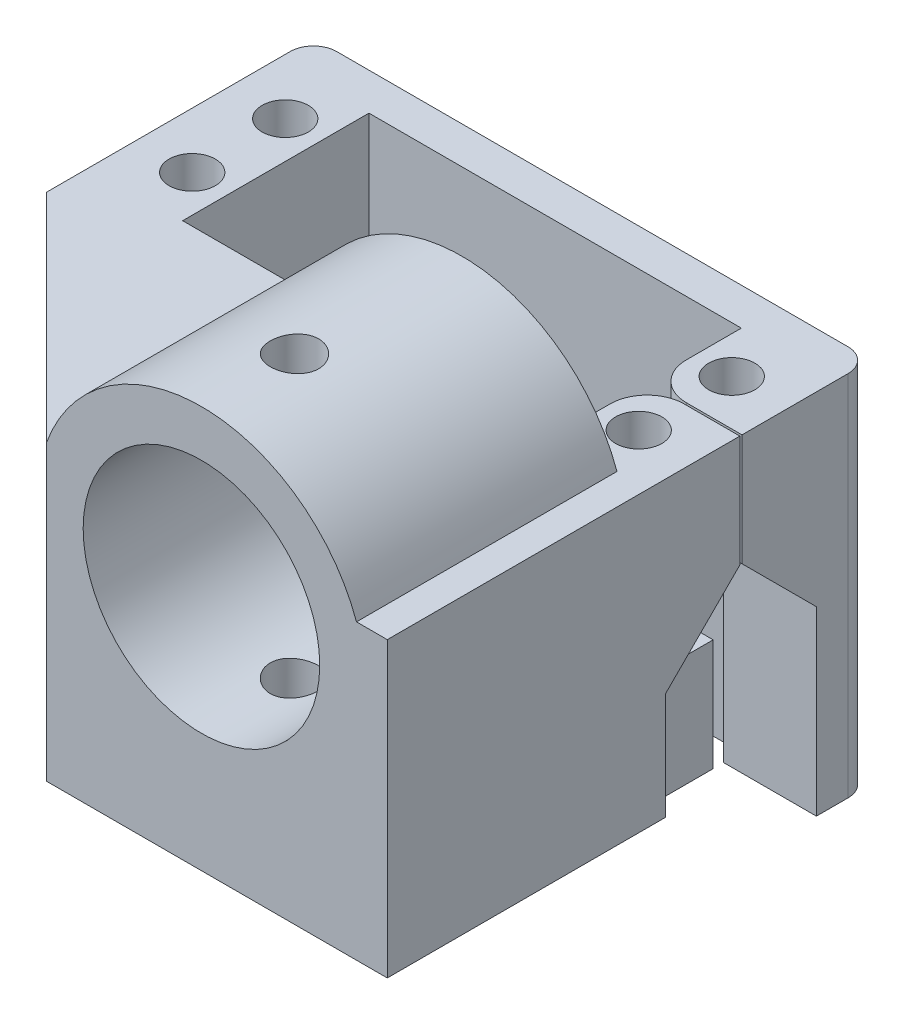
SolidWorks part; units mm, degrees
ref_plane "Front Plane" through (0, 0, 0) normal (0, 0, 1) x (1, 0, 0)
ref_plane "Top Plane" through (0, 0, 0) normal (0, 1, 0) x (1, 0, 0)
ref_plane "Right Plane" through (0, 0, 0) normal (1, 0, 0) x (0, 0, -1)
sketch "Sketch1" plane through (0, 0, 0) normal (0, 1, 0) x (1, 0, 0)
  line L0 (20.015, 0) -> (27.985, 0)
  line L1 (27.985, -14.015) -> (-27.985, -14.015)
  line L2 (27.985, -14.015) -> (27.985, 14.015)
  line L3 (27.985, 14.015) -> (-27.985, 14.015)
  line L4 (-27.985, -14.015) -> (-27.985, 14.015)
  line L5 (27.985, -14.015) -> (-27.985, 14.015) construction
  line L6 (27.985, 14.015) -> (-27.985, -14.015) construction
  line L7 (20.015, -10.015) -> (-20.015, -10.015)
  line L8 (20.015, -10.015) -> (20.015, 10.015)
  line L9 (20.015, 10.015) -> (-20.015, 10.015)
  line L10 (-20.015, -10.015) -> (-20.015, 10.015)
  line L11 (20.015, -10.015) -> (-20.015, 10.015) construction
  line L12 (20.015, 10.015) -> (-20.015, -10.015) construction
  line L13 (24, -5) -> (-24, -5) construction
  line L14 (24, -5) -> (24, 5) construction
  line L15 (24, 5) -> (-24, 5) construction
  line L16 (-24, -5) -> (-24, 5) construction
  line L17 (24, -5) -> (-24, 5) construction
  line L18 (24, 5) -> (-24, -5) construction
  line L19 (-27.985, -14.015) -> (-27.985, -18.015)
  line L20 (-27.985, -18.015) -> (27.985, -18.015)
  line L21 (27.985, -18.015) -> (27.985, -14.015)
  line L22 (27.985, 14.015) -> (29.985, 14.015)
  line L23 (29.985, 14.015) -> (29.985, 0.115)
  line L24 (29.985, 0.115) -> (24, 0.115)
  line L25 (27.985, -14.015) -> (29.985, -14.015)
  line L26 (29.985, -14.015) -> (29.985, -0.115)
  line L27 (29.985, -0.115) -> (24, -0.115)
  line L28 (27.985, -18.015) -> (29.985, -18.015)
  line L29 (29.985, -18.015) -> (29.985, -14.015)
  line L30 (-27.985, 14.015) -> (-29.985, 14.015)
  line L31 (-29.985, 14.015) -> (-29.985, -18.015)
  line L32 (-29.985, -18.015) -> (-27.985, -18.015)
  line L33 (-20.015, -18.015) -> (-20.015, -78.515)
  line L34 (-20.015, -78.515) -> (17.515, -78.515)
  line L35 (17.515, -78.515) -> (17.515, -88.485)
  line L36 (17.515, -88.485) -> (-29.985, -88.485)
  line L37 (-29.985, -88.485) -> (-29.985, -18.015)
  line L38 (-20.015, -78.515) -> (-29.985, -78.515) construction
  line L39 (-37.485, 7.6) -> (-29.985, 7.6)
  line L40 (-37.485, -7.6) -> (-29.985, -7.6)
  line L41 (-37.485, 0) -> (-29.985, 0) construction
  circle A1 centre (24, 5) radius 2.485
  circle A2 centre (24, -5) radius 2.485
  circle A3 centre (-24, -5) radius 2.485
  circle A4 centre (-24, 5) radius 2.485
  arc A5 (20.015, 4.1) -> (27.985, 4.1) centre (24, 4.1) ccw
  arc A6 (20.015, -4.1) -> (27.985, -4.1) centre (24, -4.1) cw
  circle A7 centre (-37.485, 0) radius 2.6
  arc A8 (-37.485, 7.6) -> (-37.485, -7.6) centre (-37.485, 0) ccw
  point P0 (0, 0)
  point P6 (0, 0)
  point P11 (0, 0)
  dimension "D1" = 4.97
  dimension "D7" = 4.1
  dimension "D8" = 4.1
  dimension "D14" = 5.2
  dimension "D15" = 5
  dimension "D16" = 7.5
  dimension "D2" = 48
  dimension "D3" = 4
  dimension "D4" = 40.03
  dimension "D5" = 20.03
  dimension "D6" = 10
  dimension "D9" = 4
  dimension "D10" = 2
  dimension "D11" = 2
  dimension "D12" = 60.5
  dimension "D13" = 47.5
extrude "Boss-Extrude1" add sketch "Sketch1" along normal mid plane 12 contours A6 L8 L7 L10 L9 A5 L2 L3 L4 L1 A4 A3 A2 A1 | L20 L21 L1 L19 | L24 L23 L22 L2 | L26 L27 L2 L25 | L27 A6 L2 | A5 L24 L2 | L28 L29 L25 L21 | L31 L32 L19 L4 L30 region at (21.6248, 0, 1.7248) region at (28.985, 0, 7.065) region at (27.0949, 0, 1.0051) region at (27.0949, 0, -1.0051) region at (28.985, 0, -7.065) region at (0, 0, 16.015) region at (28.985, 0, 16.015) region at (-28.985, 0, 2)
sketch "Sketch2" plane through (0, -6, 0) normal (0, -1, 0) x (1, 0, 0)
  circle A0 centre (24, -5) radius 2.485 construction
  circle A1 centre (24, 5) radius 2.485 construction
  circle A2 centre (-24, -5) radius 2.485 construction
  circle A3 centre (-24, 5) radius 2.485 construction
  circle A4 centre (24, -5) radius 2.485
  circle A5 centre (24, 5) radius 2.485
  circle A6 centre (-24, -5) radius 2.485
  circle A7 centre (-24, 5) radius 2.485
extrude "Boss-Extrude2" add sketch "Sketch2" against normal offset from surface (2 mm away) 10 up to face at (10.4535, 6, 0.5714)
sketch "Sketch3" plane through (0, 0, 18.015) normal (0, 0, 1) x (1, 0, 0)
  line L0 (10.015, 0) -> (-10.485, 0) construction
  line L1 (-10.485, 0) -> (-14.485, 0) construction
  circle A2 centre (10.015, 0) radius 1.6
  circle A3 centre (-14.485, 0) radius 1.6
  dimension "D3" = 3.2
  dimension "D4" = 3.2
  dimension "D1" = 4
  dimension "D2" = 20.5
  dimension "D5" = 10
extrude "Cut-Extrude1" [suppressed] cut sketch "Sketch3" against normal blind 10 contours A2
sketch "Sketch4" [suppressed] plane through (0, 0, -14.015) normal (0, 0, -1) x (-1, 0, 0)
  line L4 (-29.985, -6) -> (29.985, -6)
  line L5 (29.985, -6) -> (29.985, 6)
  line L6 (29.985, 6) -> (-29.985, 6)
  line L7 (-29.985, 6) -> (-29.985, -6)
  line L8 (-29.985, -6) -> (29.985, -6)
  line L10 (29.985, 6) -> (-29.985, 6)
  line L12 (-29.985, 6) -> (-29.985, -6)
  line L13 (29.985, -6) -> (29.985, 6)
  circle A2 centre (-10.015, 0) radius 3
  circle A6 centre (-10.015, 0) radius 1.6 construction
  circle A7 centre (-10.015, 0) radius 1.6 construction
  dimension "D2" = 6
  dimension "D1" = 0
extrude "Cut-Extrude2" [suppressed] cut sketch "Sketch4" against normal offset from surface (28.03 mm away) 4 contours A2 offset beyond the face yes
sketch "Sketch5" plane through (0, 0, 0) normal (1, 0, 0) x (0, 0, -1)
  line L0 (-18.015, -6) -> (-10.015, -6)
  line L1 (-10.015, -6) -> (-10.015, -21.5)
  line L2 (-10.015, -21.5) -> (6.985, -21.5)
  line L3 (6.985, -21.5) -> (6.985, -33.5)
  line L4 (6.985, -33.5) -> (-18.015, -33.5)
  line L5 (-18.015, -33.5) -> (-18.015, -6)
  line L7 (-10.015, 6) -> (10.015, 6) construction
  dimension "D1" = 27.5
  dimension "D2" = 12
  dimension "D3" = 25
extrude "Boss-Extrude3" add sketch "Sketch5" along normal up to surface (20.015 mm away) up to face at (20.015, 0, 7.0575)
sketch "Sketch6" plane through (0, -33.5, 0) normal (0, -1, 0) x (1, 0, 0)
  line L0 (0, 0) -> (10.015, 0) construction
  line L1 (20.015, -4.1) -> (20.015, -10.015) construction
  circle A0 centre (10.015, 0) radius 2.485
  dimension "D2" = 4.97
  dimension "D1" = 10
extrude "Cut-Extrude3" cut sketch "Sketch6" against normal blind 10
sketch "Sketch10" plane through (0, 0, 18.015) normal (0, 0, 1) x (1, 0, 0)
  circle A0 centre (-14.485, 0) radius 1.485
  dimension "D1" = 2.97
extrude "Cut-Extrude6" [suppressed] cut sketch "Sketch10" against normal offset from surface 2 and the other way through all
sketch "Sketch11" plane through (0, 0, 18.015) normal (0, 0, 1) x (1, 0, 0)
  line L1 (10.0075, 0) -> (10.0075, 17.715) construction
  line L2 (20.015, -33.5) -> (20.015, -6) construction
  line L3 (0, -6) -> (0, -33.5) construction
  line L4 (10.0075, 0) -> (-7.7075, 0) construction
  line L5 (-29.985, 6) -> (29.985, 6) construction
  line L6 (-29.985, -6) -> (0, -6) construction
  circle A0 centre (10.0075, 0) radius 12.715
  circle A1 centre (10.0075, 0) radius 17.715
  line M2 (0, -6) -> (0, -33.5)
  line M4 (20.015, -33.5) -> (20.015, -6)
  line M8 (29.985, 6) -> (-29.985, 6)
  line M10 (-29.985, -6) -> (0, -6)
  dimension "D1" = 25.43
  dimension "D2" = 5
extrude "Boss-Extrude4" add sketch "Sketch11" against normal up to surface (8 mm away) contours A0 M2 M4 | A1 A0 M2 M4 | A0 M4 | A1 A0 M4 | L1 A0 A1 | A0 M2 | A1 A0 M10 M2 | A0 L1 A1 M10 | A0 M8 | A1 A0 M8 region at (10.0383, -2.3315, 18.015) region at (24.003, -3.2734, 18.015) region at (10.0075, 8.7579, 18.015) region at (10.0075, 13.0683, 18.015) region at (10.0075, -13.879, 18.015) region at (-4.7808, 0, 18.015) region at (-2.5393, -9.2557, 18.015) region at (-0.4138, -6.6334, 18.015) up to face at (2.8593, -7, 10.015)
extrude "Boss-Extrude5" add sketch "Sketch11<3>" along normal blind 20 contours A1 A0 M2 M4 | A1 A0 M4 | L1 A0 A1 | A0 L1 A1 M10 | A1 A0 M10 M2 | A1 A0 M8 region at (24.003, -3.2734, 18.015) region at (10.0075, 13.0683, 18.015) region at (10.0075, -13.879, 18.015) region at (-4.7808, 0, 18.015) region at (-2.5393, -9.2557, 18.015)
sketch "Sketch11<3>" plane through (0, 0, 18.015) normal (0, 0, 1) x (1, 0, 0) same geometry as "Sketch11"
sketch "Sketch12" plane through (0, -33.5, 0) normal (0, -1, 0) x (1, 0, 0)
  line L0 (-6.6605, 10.015) -> (-20.015, 10.015) construction
  line L1 (-7.7075, 38.015) -> (27.7225, 38.015)
  line L2 (-7.7075, 38.015) -> (-7.7075, 10.015)
  line L3 (-7.7075, 10.015) -> (27.7225, 10.015)
  line L4 (27.7225, 38.015) -> (27.7225, 10.015)
extrude "Boss-Extrude6" [suppressed] add sketch "Sketch12" against normal up to surface (33.5 mm away)
sketch "Sketch13" plane through (0, 0, 38.015) normal (0, 0, 1) x (1, 0, 0)
  line L3 (0, -14.6175) -> (0, -33.5)
  line L4 (0, -33.5) -> (20.015, -33.5)
  line L5 (20.015, -33.5) -> (20.015, -14.6175)
  line L6 (0, -14.6175) -> (0, -33.5)
  line L7 (0, -33.5) -> (20.015, -33.5)
  line L8 (20.015, -33.5) -> (20.015, -14.6175)
  line L9 (-6.6605, 6) -> (-29.985, 6)
  line L10 (-29.985, 6) -> (-29.985, -6)
  line L11 (-29.985, -6) -> (-6.6605, -6)
  line L12 (-6.6605, 6) -> (-29.985, 6)
  line L13 (-29.985, 6) -> (-29.985, -6)
  line L14 (-29.985, -6) -> (-6.6605, -6)
  line L15 (26.6755, -6) -> (29.985, -6)
  line L16 (29.985, -6) -> (29.985, 6)
  line L17 (29.985, 6) -> (26.6755, 6)
  line L18 (26.6755, -6) -> (29.985, -6)
  line L19 (29.985, -6) -> (29.985, 6)
  line L20 (29.985, 6) -> (26.6755, 6)
  circle A1 centre (10.0075, 0) radius 17.715
  circle A2 centre (10.0075, 0) radius 17.715
  arc A3 (0, -14.6175) -> (20.015, -14.6175) centre (10.0075, 0) ccw
  arc A4 (0, -14.6175) -> (20.015, -14.6175) centre (10.0075, 0) ccw
  arc A5 (-6.6605, 6) -> (-6.6605, -6) centre (10.0075, 0) ccw
  arc A6 (-6.6605, 6) -> (-6.6605, -6) centre (10.0075, 0) ccw
  arc A7 (26.6755, -6) -> (26.6755, 6) centre (10.0075, 0) ccw
  arc A8 (26.6755, -6) -> (26.6755, 6) centre (10.0075, 0) ccw
  circle M6 centre (10.0075, 0) radius 17.715
  dimension "D1" = 0
  dimension "D2" = 0
  dimension "D3" = 0
  dimension "D4" = 0
extrude "Boss-Extrude7" add sketch "Sketch13" against normal up to surface (20 mm away) contours L7 L8 L6 M6 | L13 L14 L12 M6 | L19 L20 L18 M6 region at (10.0075, -25.0861, 38.015) region at (-18.6717, 0, 38.015) region at (28.6628, 0, 38.015) up to face at (10.0075, -24.8331, 18.015)
sketch "Sketch14" plane through (0, 6, 0) normal (0, 1, 0) x (1, 0, 0)
  line L0 (-6.6605, -38.015) -> (-29.985, -14.6905)
  line L1 (-29.985, 14.015) -> (-29.985, -38.015) construction
  line L2 (-6.6605, -38.015) -> (-29.985, -38.015) construction
  line L3 (-6.6605, -38.015) -> (-29.985, -38.015)
  line L4 (-29.985, 14.015) -> (-29.985, -38.015)
  line M11 (-29.985, 14.015) -> (-29.985, -38.015)
  line M12 (-29.985, -38.015) -> (-6.6605, -38.015)
  dimension "D1" = 45
extrude "Cut-Extrude7" cut sketch "Sketch14" against normal through all both and the other way through all contours L0 M12 M11 region at (-22.2102, 6, 30.2402)
sketch "Sketch15" plane through (20.015, 0, 0) normal (1, 0, 0) x (0, 0, -1)
  line L0 (-38.015, -14.6175) -> (-19.1325, -33.5)
  line L1 (6.985, -33.5) -> (-38.015, -33.5) construction
  line L2 (-38.015, -33.5) -> (-38.015, -14.6175) construction
  line L3 (6.985, -33.5) -> (-38.015, -33.5)
  line L4 (-38.015, -33.5) -> (-38.015, -14.6175)
  line M5 (-38.015, -14.6175) -> (-38.015, -33.5)
  line M6 (-38.015, -33.5) -> (6.985, -33.5)
  dimension "D1" = 45
extrude "Cut-Extrude8" cut sketch "Sketch15" against normal through all both contours L0 M5 M6 region at (20.015, -27.2058, 31.7208)
fillet "Fillet1" radius 2.5 2 edges at (29.985, 0, -14.015) (-29.985, 0, -14.015)
sketch "Sketch16" plane through (0, 0, 0) normal (0, 1, 0) x (1, 0, 0)
  line L0 (-2.7075, -38.015) -> (22.7225, -38.015) construction
  line L1 (-2.7075, -18.015) -> (22.7225, -18.015) construction
  line L2 (-2.7075, -38.015) -> (22.7225, -38.015)
  line L3 (-2.7075, -18.015) -> (22.7225, -18.015)
  line L4 (10.0075, -18.015) -> (10.0075, -38.015) construction
  circle A0 centre (10.0075, -28.015) radius 2.6
  dimension "D1" = 5.2
extrude "Cut-Extrude9" cut sketch "Sketch16" against normal through all both and the other way through all contours A0
sketch "Sketch17" plane through (0, -33.5, 0) normal (0, -1, 0) x (1, 0, 0)
  circle A0 centre (10.0075, 28.015) radius 5.4369
  circle A1 centre (10.0075, 28.015) radius 2.6 construction
  circle A2 centre (10.0075, 28.015) radius 2.6
extrude "Cut-Extrude10" cut sketch "Sketch17" against normal blind 12
sketch "Sketch18" plane through (0, -33.5, 0) normal (0, -1, 0) x (1, 0, 0)
  line L0 (26.6755, 38.015) -> (20.015, 38.015) construction
  line L1 (20.015, 38.015) -> (20.015, 10.015) construction
  line L2 (20.015, 10.015) -> (26.6755, 10.015) construction
  line L3 (0, 19.1325) -> (20.015, 19.1325) construction
  line L4 (20.015, 19.1325) -> (20.015, 38.015) construction
  line L5 (20.015, 38.015) -> (0, 38.015) construction
  line L6 (0, 38.015) -> (0, 19.1325) construction
  line L7 (0, 38.015) -> (-6.6605, 38.015) construction
  line L8 (-6.6605, 10.015) -> (0, 10.015) construction
  line L9 (0, 10.015) -> (0, 38.015) construction
  line L10 (-27.485, -14.015) -> (27.485, -14.015) construction
  line L11 (29.985, -11.515) -> (29.985, -0.115) construction
  line L12 (29.985, -0.115) -> (24, -0.115) construction
  line L13 (20.015, -4.1) -> (20.015, -10.015) construction
  line L14 (20.015, -10.015) -> (-20.015, -10.015) construction
  line L15 (-20.015, -10.015) -> (-20.015, 10.015) construction
  line L16 (-20.015, 10.015) -> (-6.6605, 10.015) construction
  line L17 (-6.6605, 38.015) -> (-29.985, 14.6905) construction
  line L18 (-29.985, 14.6905) -> (-29.985, -11.515) construction
  line L19 (29.985, 0.115) -> (29.985, 38.015) construction
  line L20 (29.985, 38.015) -> (26.6755, 38.015) construction
  line L21 (26.6755, 10.015) -> (20.015, 10.015) construction
  line L22 (20.015, 10.015) -> (20.015, 4.1) construction
  line L23 (24, 0.115) -> (29.985, 0.115) construction
  line L24 (26.6755, 38.015) -> (20.015, 38.015)
  line L25 (20.015, 38.015) -> (20.015, 10.015)
  line L26 (20.015, 10.015) -> (26.6755, 10.015)
  line L27 (0, 19.1325) -> (20.015, 19.1325)
  line L28 (20.015, 19.1325) -> (20.015, 38.015)
  line L29 (20.015, 38.015) -> (0, 38.015)
  line L30 (0, 38.015) -> (0, 19.1325)
  line L31 (0, 38.015) -> (-6.6605, 38.015)
  line L32 (-6.6605, 10.015) -> (0, 10.015)
  line L33 (0, 10.015) -> (0, 38.015)
  line L34 (-27.485, -14.015) -> (27.485, -14.015)
  line L35 (29.985, -11.515) -> (29.985, -0.115)
  line L36 (29.985, -0.115) -> (24, -0.115)
  line L37 (20.015, -4.1) -> (20.015, -10.015)
  line L38 (20.015, -10.015) -> (-20.015, -10.015)
  line L39 (-20.015, -10.015) -> (-20.015, 10.015)
  line L40 (-20.015, 10.015) -> (-6.6605, 10.015)
  line L41 (-6.6605, 38.015) -> (-29.985, 14.6905)
  line L42 (-29.985, 14.6905) -> (-29.985, -11.515)
  line L43 (29.985, 0.115) -> (29.985, 38.015)
  line L44 (29.985, 38.015) -> (26.6755, 38.015)
  line L45 (26.6755, 10.015) -> (20.015, 10.015)
  line L46 (20.015, 10.015) -> (20.015, 4.1)
  line L47 (24, 0.115) -> (29.985, 0.115)
  line L48 (20.015, 8.115) -> (29.985, 8.115)
  line L50 (29.985, -8.115) -> (20.015, -8.115)
  arc A0 (27.485, -14.015) -> (29.985, -11.515) centre (27.485, -11.515) ccw construction
  arc A1 (24, -0.115) -> (20.015, -4.1) centre (24, -4.1) ccw construction
  arc A2 (-29.985, -11.515) -> (-27.485, -14.015) centre (-27.485, -11.515) ccw construction
  arc A3 (20.015, 4.1) -> (24, 0.115) centre (24, 4.1) ccw construction
  arc A4 (27.485, -14.015) -> (29.985, -11.515) centre (27.485, -11.515) ccw
  arc A5 (24, -0.115) -> (20.015, -4.1) centre (24, -4.1) ccw
  arc A6 (-29.985, -11.515) -> (-27.485, -14.015) centre (-27.485, -11.515) ccw
  arc A7 (20.015, 4.1) -> (24, 0.115) centre (24, 4.1) ccw
  circle A8 centre (10.0075, 28.015) radius 5.4369
  arc A9 (5.5532, 31.1325) -> (14.4618, 31.1325) centre (10.0075, 28.015) ccw construction
  line M6 (20.015, 19.1325) -> (0, 19.1325)
  line M7 (0, 19.1325) -> (0, -6.985)
  line M9 (20.015, -6.985) -> (20.015, 19.1325)
  dimension "D1" = 8
  dimension "D2" = 8
extrude "Boss-Extrude8" add sketch "Sketch18" against normal up to next contours L42 A6 L34 A4 L35 L50 L37 L38 L39 L40 L32 L30 L31 L41 M9 M7 | L46 L48 L43 L44 L24 L25 M9 | L29 L30 L25 A8 M6 region at (25, -33.5, 23.065) region at (19.7398, -33.5, 28.5737) region at (-0.7939, -33.5, 28.5737)
chamfer "Chamfer1" distance 8 angle 45 2 edges at (25, -6, -8.115) (25, -6, 8.115)
chamfer "Chamfer2" distance 8 angle 45 3 edges at (-18.3227, -33.5, 26.3527) (11.6623, -33.5, 38.015) (29.985, -33.5, 23.065)
